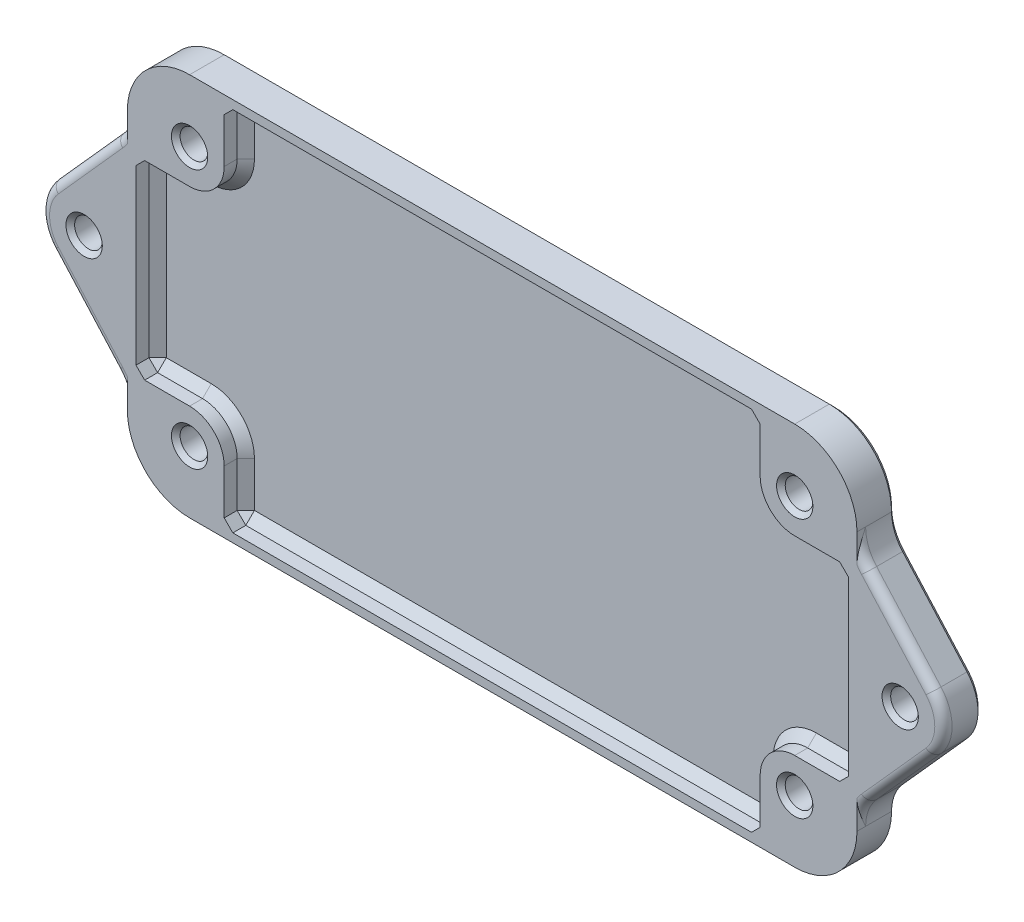
SolidWorks part; units mm, degrees
ref_plane "Спереди" through (0, 0, 0) normal (0, 0, 1) x (1, 0, 0)
ref_plane "Сверху" through (0, 0, 0) normal (0, 1, 0) x (1, 0, 0)
ref_plane "Справа" through (0, 0, 0) normal (1, 0, 0) x (0, 0, -1)
sketch "Эскиз1" plane through (0, 0, 0) normal (0, 0, 1) x (1, 0, 0)
  line L24 (42.2, -15) -> (42.2, 15)
  line L25 (35, 15) -> (-35, 15) construction
  line L26 (35, 15) -> (35, -15) construction
  line L27 (35, -15) -> (-35, -15) construction
  line L28 (-35, 15) -> (-35, -15) construction
  line L29 (35, 15) -> (-35, -15) construction
  line L30 (35, -15) -> (-35, 15) construction
  line L31 (35, 22.2) -> (-35, 22.2)
  line L32 (-42.2, 15) -> (-42.2, -15)
  line L33 (-35, -22.2) -> (35, -22.2)
  arc A0 (42.2, -15) -> (35, -22.2) centre (35, -15) cw
  arc A2 (-35, -22.2) -> (-42.2, -15) centre (-35, -15) cw
  arc A3 (-42.2, 15) -> (-35, 22.2) centre (-35, 15) cw
  arc A4 (42.2, 15) -> (35, 22.2) centre (35, 15) ccw
  point P0 (0, 0)
  dimension "D3" = 7.2
  dimension "D1" = 30
  dimension "D2" = 70
extrude "Бобышка-Вытянуть1" add sketch "Эскиз1" along normal blind 4.5
sketch "Эскиз2" plane through (0, 0, 4.5) normal (0, 0, 1) x (1, 0, 0)
  line L0 (31, -15) -> (31, -21.2)
  line L1 (35, 15) -> (-35, 15) construction
  line L2 (35, 15) -> (35, -15) construction
  line L3 (35, -15) -> (-35, -15) construction
  line L4 (-35, 15) -> (-35, -15) construction
  line L5 (35, 15) -> (-35, -15) construction
  line L6 (35, -15) -> (-35, 15) construction
  line L7 (31, -21.2) -> (-31, -21.2)
  line L8 (-31, -21.2) -> (-31, -15)
  line L9 (-35, -11) -> (-41.2, -11)
  line L10 (-41.2, -11) -> (-41.2, 11)
  line L11 (-41.2, 11) -> (-35, 11)
  line L12 (-31, 15) -> (-31, 21.2)
  line L13 (-31, 21.2) -> (31, 21.2)
  line L14 (31, 21.2) -> (31, 15)
  line L15 (35, 11) -> (41.2, 11)
  line L16 (41.2, 11) -> (41.2, -11)
  line L17 (41.2, -11) -> (35, -11)
  line L18 (42.2, -15) -> (42.2, 15) construction
  circle A0 centre (35, -15) radius 1.6
  circle A1 centre (-35, -15) radius 1.6
  circle A2 centre (-35, 15) radius 1.6
  circle A3 centre (35, 15) radius 1.6
  arc A4 (31, -15) -> (35, -11) centre (35, -15) cw
  arc A5 (35, 11) -> (31, 15) centre (35, 15) cw
  arc A6 (-35, 11) -> (-31, 15) centre (-35, 15) ccw
  arc A7 (-31, -15) -> (-35, -11) centre (-35, -15) ccw
  point P0 (0, 0)
  dimension "D3" = 3.2
  dimension "D4" = 4
  dimension "D1" = 30
  dimension "D2" = 70
  dimension "D5" = 1
extrude "Вырез-Вытянуть1" cut sketch "Эскиз2" against normal blind 2.5 contours L17 A4 L0 L7 L8 A7 L9 L10 L11 A6 L12 L13 L14 A5 L15 L16
extrude "Вырез-Вытянуть2" cut sketch "Эскиз2<3>" against normal through all contours A1 | A3 | A0 | A2 region at (-35, -15, 4.5) region at (35, 15, 4.5)
sketch "Эскиз2<3>" plane through (0, 0, 4.5) normal (0, 0, 1) x (1, 0, 0) same geometry as "Эскиз2"
hole_wizard "Зенковка для  винта с потайной головкой с внутренним шестигранником M31" positions "Эскиз4" profile "Эскиз3" countersink size "M3" standard "Ansi Metric" end condition through all
sketch "Эскиз4" plane through (0, 0, 0) normal (0, 0, -1) x (-1, 0, 0)
  point P0 (-35, 15)
  point P3 (-35, -15)
  point P6 (35, -15)
  point P9 (35, 15)
sketch "Эскиз3" plane through (35, 15, 0) normal (1, 0, 0) x (0, 1, 0)
  line L0 (0, 0) -> (0, 4.5)
  line L1 (0, 4.5) -> (1.6, 4.5)
  line L2 (1.6, 4.5) -> (1.6, 1.5)
  line L3 (1.6, 1.5) -> (3.1, 0)
  line L5 (3.1, 0) -> (0, 0)
  line L6 (-1.6, 1.5) -> (-3.1, 0) construction
  line L11 (0, -6.35) -> (0, 107.95) construction
  dimension "Диаметр сквозного отверстия" = 3.2
  dimension "Глубина сквозного отверстия" = 4.5
  dimension "Диаметр передней зенковки" = 6.2
  dimension "Угол передней зенковки" = 90
sketch "Эскиз7" plane through (0, 0, 0) normal (0, 0, 1) x (1, 0, 0)
  line L0 (43.4732, -11.6667) -> (50.9268, -3.3333)
  line L1 (50.9268, 3.3333) -> (43.4732, 11.6667)
  line L2 (42.2, -15) -> (42.2, 15) construction
  line L3 (0, -35.3697) -> (0, 37.1902) construction
  line L4 (42.2, -15) -> (42.2, 15)
  line L5 (-42.2, -15) -> (-42.2, 15)
  line L6 (-50.9268, 3.3333) -> (-43.4732, 11.6667)
  line L7 (-43.4732, -11.6667) -> (-50.9268, -3.3333)
  arc A0 (42.2, -15) -> (43.4732, -11.6667) centre (47.2, -15) cw
  arc A1 (42.2, 15) -> (43.4732, 11.6667) centre (47.2, 15) ccw
  arc A2 (50.9268, -3.3333) -> (50.9268, 3.3333) centre (47.2, 0) ccw
  circle A3 centre (47.2, 0) radius 1.6
  circle A4 centre (-47.2, 0) radius 1.6
  arc A5 (-50.9268, -3.3333) -> (-50.9268, 3.3333) centre (-47.2, 0) cw
  arc A6 (-42.2, 15) -> (-43.4732, 11.6667) centre (-47.2, 15) cw
  arc A7 (-42.2, -15) -> (-43.4732, -11.6667) centre (-47.2, -15) ccw
  dimension "D1" = 5
  dimension "D2" = 3.2
  dimension "D3" = 5
  dimension "D4" = 5
extrude "Бобышка-Вытянуть2" add sketch "Эскиз7" along normal blind 4.5 separate body
fillet "Скругление1" radius 1 5 edges at (42.5291, -13.2159, 4.5) (47.2, -7.5, 4.5) (42.5291, 13.2159, 4.5) (47.2, 7.5, 4.5) (52.2, 0, 4.5)
fillet "Скругление2" radius 1 5 edges at (-42.5291, 13.2159, 4.5) (-47.2, 7.5, 4.5) (-42.5291, -13.2159, 4.5) (-47.2, -7.5, 4.5) (-52.2, 0, 4.5)
combine bodies "Соединить1" operation type add bodies to combine 117 122 123
chamfer "Фаска1" distance 0.5 angle 45 24 edges at (0, -22.2, 0) (40.0912, -20.0912, 0) (-40.0912, -20.0912, 0) (42.5291, -13.2159, 0) (-42.5291, -13.2159, 0) (47.2, -7.5, 0) (-47.2, -7.5, 0) (52.2, 0, 0) (-52.2, 0, 0) (47.2, 7.5, 0) (-47.2, 7.5, 0) (42.5291, 13.2159, 0) (-42.5291, 13.2159, 0) (40.0912, 20.0912, 0) (-40.0912, 20.0912, 0) (0, 22.2, 0) (-48.8, 0, 4.5) (-33.4, -15, 4.5) (-33.4, 15, 4.5) (36.6, 15, 4.5) (36.6, -15, 4.5) (48.8, 0, 4.5) (-48.8, 0, 0) (48.8, 0, 0)
chamfer "Фаска2" distance 1 angle 45 24 edges at (-31, -18.1, 2) (-38.1, -11, 2) (-32.1716, -12.1716, 2) (-41.2, 0, 2) (-38.1, 11, 2) (-31, 18.1, 2) (-32.1716, 12.1716, 2) (0, 21.2, 2) (38.1, 11, 2) (31, 18.1, 2) (32.1716, 12.1716, 2) (41.2, 0, 2) (31, -18.1, 2) (38.1, -11, 2) (32.1716, -12.1716, 2) (0, -21.2, 2) (-41.2, 11, 3.25) (-41.2, -11, 3.25) (31, 21.2, 3.25) (-31, 21.2, 3.25) (41.2, 11, 3.25) (41.2, -11, 3.25) (-31, -21.2, 3.25) (31, -21.2, 3.25)
